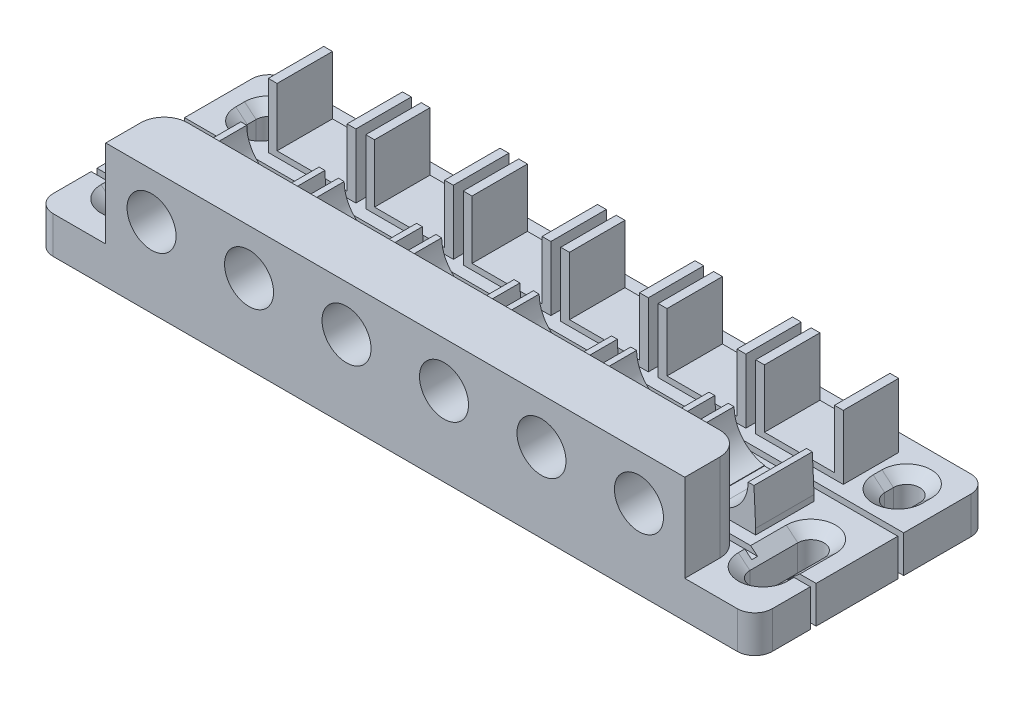
SolidWorks part; units mm, degrees
ref_plane "Front Plane" through (0, 0, 0) normal (0, 0, 1) x (1, 0, 0)
ref_plane "Top Plane" through (0, 0, 0) normal (0, 1, 0) x (1, 0, 0)
ref_plane "Right Plane" through (0, 0, 0) normal (1, 0, 0) x (0, 0, -1)
sketch "Sketch1" plane through (0, 0, 0) normal (0, 1, 0) x (1, 0, 0)
  line L1 (-61.6, -20) -> (0, -20)
  line L2 (-61.6, -20) -> (-61.6, 20)
  line L3 (-61.6, 20) -> (0, 20)
  line L4 (0, -20) -> (0, 20)
  line L5 (-61.6, -20) -> (0, 20) construction
  line L6 (-61.6, 20) -> (0, -20) construction
  point P0 (0, 0)
  dimension "D1" = 61.6
  dimension "D2" = 40
extrude "Boss-Extrude1" add sketch "Sketch1" along normal blind 6.35
hole_wizard "CSK SLOT for #8 Flat Head Machine Screw (100)1" positions "Sketch3" profile "Sketch2" size "#8" standard "ANSI Inch" slot yes end condition up to next
sketch "Sketch3" plane through (0, 6.35, 0) normal (0, 1, 0) x (1, 0, 0)
  line L0 (-54.6, -13.85) -> (-54.6, -1.15) construction
  line L1 (-61.6, 20) -> (-61.6, -20) construction
  line L2 (-61.6, -20) -> (0, -20) construction
  point P0 (-54.6, -7.5)
  dimension "D1" = 12.7
  dimension "D2" = 7
  dimension "D3" = 12.5
sketch "Sketch2" plane through (-54.6, 6.35, 7.5) normal (1, 0, 0) x (0, 0, 1)
  line L0 (0, 0) -> (0, 6.35)
  line L1 (0, 6.35) -> (2.2479, 6.35)
  line L2 (2.2479, 6.35) -> (2.2479, 1.6518)
  line L3 (2.2479, 1.6518) -> (4.2164, 0)
  line L5 (4.2164, 0) -> (0, 0)
  line L6 (-2.2479, 1.6518) -> (-4.2164, 0) construction
  line L11 (0, -6.35) -> (0, 107.95) construction
  dimension "Thru Hole Dia." = 4.4958
  dimension "Thru Hole Depth" = 6.35
  dimension "Near C'Sink Dia." = 8.4328
  dimension "Near C'Sink Angle" = 100
fillet "Fillet1" radius 3 2 edges at (-61.6, 3.175, 20) (-61.6, 3.175, -20)
sketch "Sketch5" plane through (0, 6.35, 0) normal (0, 1, 0) x (1, 0, 0)
  line L0 (-49.6, -20) -> (-49.6, 20) construction
  line L1 (-58.6, -20) -> (0, -20) construction
  line L2 (0, 20) -> (-58.6, 20) construction
  line L3 (-61.6, 17) -> (-61.6, -17) construction
  dimension "D1" = 12
sketch "Sketch4" plane through (0, 0, 0) normal (1, 0, 0) x (0, 0, -1)
  line L2 (-20, 6.35) -> (-10, 6.35)
  line L3 (-20, 6.35) -> (-20, 21.35)
  line L4 (-20, 21.35) -> (-10, 21.35)
  line L5 (-10, 6.35) -> (-10, 21.35)
  dimension "D1" = 10
  dimension "D2" = 15
extrude "Boss-Extrude2" add sketch "Sketch4" against normal up to vertex (49.6 mm away) up to point (-49.6, 6.35, 20)
sketch "Sketch6" plane through (0, 0, 20) normal (0, 0, 1) x (1, 0, 0)
  line L0 (-49.6, 21.35) -> (-49.6, 6.35) construction
  line L1 (-39.3254, 9.35) -> (-36.9005, 13.55) construction
  line L2 (-36.9005, 13.55) -> (-39.3254, 17.75) construction
  line L3 (-39.3254, 17.75) -> (-44.1751, 17.75) construction
  line L4 (-44.1751, 17.75) -> (-46.6, 13.55) construction
  line L5 (-46.6, 13.55) -> (-44.1751, 9.35) construction
  line L6 (-44.1751, 9.35) -> (-39.3254, 9.35) construction
  line L7 (-58.6, 6.35) -> (-49.6, 6.35) construction
  line L11 (-27.4756, 17.75) -> (-29.9005, 13.55) construction
  line L12 (-29.9005, 13.55) -> (-27.4756, 9.35) construction
  line L13 (-27.4756, 9.35) -> (-22.6259, 9.35) construction
  line L14 (-22.6259, 9.35) -> (-20.201, 13.55) construction
  line L15 (-20.201, 13.55) -> (-22.6259, 17.75) construction
  line L16 (-22.6259, 17.75) -> (-27.4756, 17.75) construction
  line L17 (-10.7762, 17.75) -> (-13.201, 13.55) construction
  line L18 (-13.201, 13.55) -> (-10.7762, 9.35) construction
  line L19 (-10.7762, 9.35) -> (-5.9264, 9.35) construction
  line L20 (-5.9264, 9.35) -> (-3.5015, 13.55) construction
  line L21 (-3.5015, 13.55) -> (-5.9264, 17.75) construction
  line L22 (-5.9264, 17.75) -> (-10.7762, 17.75) construction
  circle A0 centre (-41.7503, 13.55) radius 4.2
  circle A1 centre (-25.0508, 13.55) radius 4.2
  circle A2 centre (-8.3513, 13.55) radius 4.2
  point P1 (-49.6, 13.85)
  dimension "D1" = 8.4
  dimension "D2" = 3
  dimension "D3" = 3
  dimension "D4" = 7
  dimension "D5" = 7
extrude "Cut-Extrude1" cut sketch "Sketch6" against normal blind 9
sketch "Sketch7" plane through (0, 0, 10) normal (0, 0, -1) x (-1, 0, 0)
  circle A0 centre (8.3513, 13.55) radius 3
  circle A1 centre (25.0508, 13.55) radius 3
  circle A2 centre (41.7503, 13.55) radius 3
  dimension "D1" = 6
extrude "Cut-Extrude2" cut sketch "Sketch7" against normal through all both and the other way through all
fillet "Fillet3" radius 4 1 edges at (-49.6, 13.85, 10)
sketch "Ball Cut Plane Distance Setter Sketch" plane through (0, 6.35, 0) normal (0, 1, 0) x (1, 0, 0)
  line L0 (0, -10) -> (-61.6, -10) construction
  line L1 (0, -10) -> (0, 20) construction
  line L2 (-61.6, 17) -> (-61.6, -17) construction
  line L3 (-45.6, -10) -> (0, -10) construction
sketch "Ball Cut Plane Slave" plane through (0, 0, 0) normal (0, -1, 0) x (1, 0, 0)
  line L0 (0, 10) -> (-61.6, 10) construction
  line L1 (0, 10) -> (-61.6, 10) construction
ref_plane "Ball Cut Plane" through (0, 0, 10) normal (0, 0, -1) x (-1, 0, 0)
sketch "Sketch13" plane through (0, 0, 10) normal (0, 0, -1) x (-1, 0, 0)
  line L0 (0, 6.35) -> (61.6, 6.35)
  line L1 (61.6, 6.35) -> (61.6, 0)
sketch "Sketch15" plane through (0, 0, 0) normal (1, 0, 0) x (0, 0, -1)
  line L0 (-10, 6.35) -> (20, 6.35) construction
  line L1 (-10.5, 5.35) -> (-9.5, 5.35)
  line L2 (-10.5, 5.35) -> (-10.5, 6.35)
  line L3 (-10.5, 6.35) -> (-9.5, 6.35) construction
  line L4 (-9.5, 5.35) -> (-9.5, 6.35)
  line L5 (-10.5, 5.35) -> (-9.5, 6.35) construction
  line L6 (-10.5, 6.35) -> (-9.5, 5.35) construction
  line L7 (-10, 5.35) -> (-10, 6.35) construction
  line L8 (-10.5, 6.35) -> (-9.5, 10.2444)
  line L9 (-9.5, 10.2444) -> (-9.5, 6.35)
  point P0 (-10, 6.35)
  dimension "D1" = 1
  dimension "D2" = 1
sweep "Cut-Sweep1" cut profiles "Sketch15" path "Sketch13"
sketch "Max Carbon Length Plane Setter" plane through (0, 6.35, 0) normal (0, 1, 0) x (1, 0, 0)
  line L0 (0, 5) -> (-61.6, 5) construction
  line L1 (0, -9.5) -> (0, 20) construction
  line L2 (-61.6, 17) -> (-61.6, -9.5) construction
  line L3 (0, -10) -> (-61.6, -10) construction
  dimension "D1" = 15
sketch "Max Carbon Length Plane Slave" plane through (0, 0, 0) normal (0, -1, 0) x (1, 0, 0)
  line L0 (0, -5) -> (-61.6, -5) construction
  line L1 (-61.6, -17) -> (-61.6, 9.5) construction
  line L2 (0, -5) -> (-61.6, -5) construction
ref_plane "Max Carbon Length Plane" through (0, 0, -5) normal (0, 0, -1) x (-1, 0, 0)
sketch "Sketch19" plane through (0, 0, -5) normal (0, 0, -1) x (-1, 0, 0)
  line L0 (0, 6.35) -> (61.6, 6.35)
  line L1 (61.6, 6.35) -> (61.6, 0)
sketch "Sketch20" plane through (0, 0, 0) normal (1, 0, 0) x (0, 0, -1)
  line L1 (4.5, 5.35) -> (5.5, 5.35)
  line L2 (4.5, 5.35) -> (4.5, 7.35)
  line L3 (4.5, 7.35) -> (5.5, 7.35)
  line L4 (5.5, 5.35) -> (5.5, 7.35)
  line L5 (4.5, 5.35) -> (5.5, 7.35) construction
  line L6 (4.5, 7.35) -> (5.5, 5.35) construction
  point P0 (5, 6.35)
  dimension "D1" = 1
  dimension "D2" = 2
sweep "Cut-Sweep2" cut profiles "Sketch20" path "Sketch19"
sketch "Sketch24" plane through (0, 0, 0) normal (0, -1, 0) x (1, 0, 0)
  line L0 (0, 10) -> (-61.6, 10) construction
  line L1 (-34.2503, 7.5) -> (-49.2503, 7.5)
  line L2 (-34.2503, 7.5) -> (-34.2503, -2.5)
  line L3 (-34.2503, -2.5) -> (-49.2503, -2.5)
  line L4 (-49.2503, 7.5) -> (-49.2503, -2.5)
  line L5 (-34.2503, -7.5) -> (-49.2503, -7.5)
  line L6 (-34.2503, -7.5) -> (-34.2503, -17)
  line L7 (-34.2503, -17) -> (-49.2503, -17)
  line L8 (-49.2503, -7.5) -> (-49.2503, -17)
  line L9 (0, -5) -> (-61.6, -5) construction
  line L10 (0, -20) -> (-58.6, -20) construction
  point P14 (-41.7503, 7.5)
  dimension "D1" = 2.5
  dimension "D2" = 2.5
  dimension "D3" = 2.5
  dimension "D4" = 3
  dimension "D5" = 15
extrude "Boss-Extrude3" add sketch "Sketch24" against normal blind 7.35
sketch "Sketch25" plane through (0, 7.35, 0) normal (0, 1, 0) x (1, 0, 0)
  line L0 (-34.2503, 7.5) -> (-49.2503, 7.5) construction
  line L1 (-35.7503, 17) -> (-34.2503, 17)
  line L2 (-35.7503, 17) -> (-35.7503, 7.5)
  line L3 (-35.7503, 7.5) -> (-34.2503, 7.5)
  line L4 (-34.2503, 17) -> (-34.2503, 7.5)
  line L5 (-47.7503, 7.5) -> (-49.2503, 7.5)
  line L6 (-47.7503, 7.5) -> (-47.7503, 17)
  line L7 (-47.7503, 17) -> (-49.2503, 17)
  line L8 (-49.2503, 7.5) -> (-49.2503, 17)
  line L9 (-49.2503, 17) -> (-34.2503, 17) construction
  dimension "D1" = 12
extrude "Boss-Extrude4" add sketch "Sketch25" along normal blind 10
sketch "Sketch26" plane through (0, 0, 0) normal (0, 0, 1) x (1, 0, 0)
  line L2 (-49.2503, 7.35) -> (-34.2503, 7.35) construction
  line L3 (-47.9503, 13.55) -> (-48.9503, 13.55)
  line L4 (-48.9503, 13.55) -> (-49.2503, 7.35)
  line L5 (-49.2503, 7.35) -> (-42.7503, 7.35)
  line L6 (-34.2503, 7.35) -> (-34.5503, 13.55)
  line L7 (-34.5503, 13.55) -> (-35.5503, 13.55)
  line L9 (-40.7503, 7.35) -> (-34.2503, 7.35)
  line L11 (-42.7503, 7.35) -> (-42.7503, 7.4312)
  line L13 (-40.7503, 7.35) -> (-40.7503, 7.4312)
  arc A0 (-40.7503, 7.4312) -> (-35.5503, 13.55) centre (-41.7503, 13.55) ccw
  circle A3 centre (-41.7503, 13.55) radius 3 construction
  arc A4 (-47.9503, 13.55) -> (-42.7503, 7.4312) centre (-41.7503, 13.55) ccw
  dimension "D1" = 12.4
  dimension "D2" = 1
extrude "Boss-Extrude5" add sketch "Sketch26" along normal up to surface (7.5 mm away) from vertex up to face at (-41.7503, 6.85, 7.5) starting at point (-34.2503, 6.35, -2.5)
pattern_linear "LPattern3" count 3 spacing 16.7 along (1, 0, 0) of "Boss-Extrude3", "Boss-Extrude4", "Boss-Extrude5"
hole_wizard "CSK SLOT for #8 Flat Head Machine Screw (100)2" positions "Sketch22" profile "Sketch21" size "#8" standard "ANSI Inch" slot yes end condition up to next
sketch "Sketch22" plane through (0, 6.35, 0) normal (0, 1, 0) x (1, 0, 0)
  line L0 (-54.6, 9.25) -> (-54.6, 15.25) construction
  line L1 (-49.2503, 7.5) -> (-49.2503, 17) construction
  point P0 (-54.6, 12.25)
  point P16 (-49.2503, 12.25)
  dimension "D1" = 6
sketch "Sketch21" plane through (-54.6, 6.35, -12.25) normal (1, 0, 0) x (0, 0, 1)
  line L0 (0, 0) -> (0, 6.35)
  line L1 (0, 6.35) -> (2.2479, 6.35)
  line L2 (2.2479, 6.35) -> (2.2479, 1.6518)
  line L3 (2.2479, 1.6518) -> (4.2164, 0)
  line L5 (4.2164, 0) -> (0, 0)
  line L6 (-2.2479, 1.6518) -> (-4.2164, 0) construction
  line L11 (0, -6.35) -> (0, 107.95) construction
  dimension "Thru Hole Dia." = 4.4958
  dimension "Thru Hole Depth" = 6.35
  dimension "Near C'Sink Dia." = 8.4328
  dimension "Near C'Sink Angle" = 100
mirror "Mirror1" about plane through (0, 6.35, 20) normal (-1, 0, 0) of bodies 113 111
sketch "Sketch27" plane through (0, 6.35, 0) normal (0, 1, 0) x (1, 0, 0)
  line L0 (54.6, -11.6021) -> (54.6, -3.3979) construction
equation "\"hexdist\"= 5mm"
equation "\"hex\"=5"
